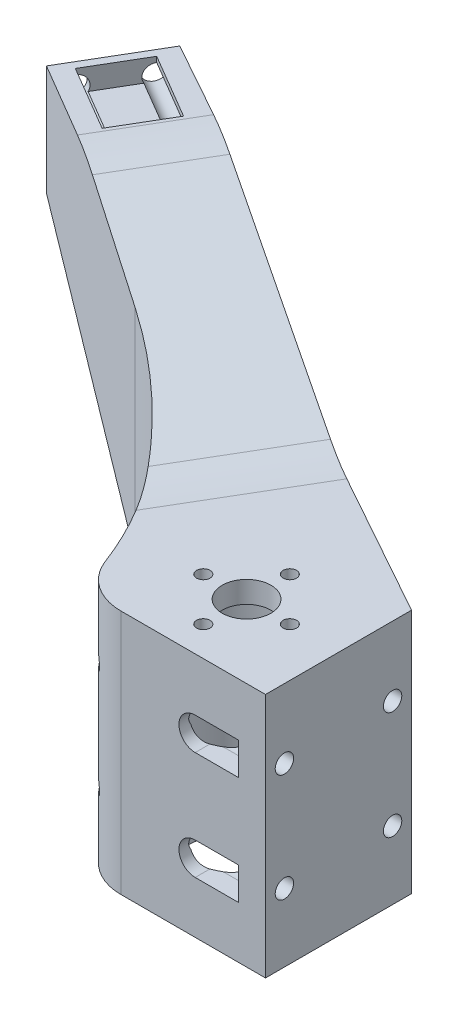
SolidWorks part; units mm, degrees
ref_plane "Front Plane" through (0, 0, 0) normal (0, 0, 1) x (1, 0, 0)
ref_plane "Top Plane" through (0, 0, 0) normal (0, 1, 0) x (1, 0, 0)
ref_plane "Right Plane" through (0, 0, 0) normal (1, 0, 0) x (0, 0, -1)
sketch "Sketch1" plane through (0, 0, 0) normal (0, 1, 0) x (1, 0, 0)
  line L0 (0, -1037.0992) -> (0, 50817.8602) construction
  line L1 (-1037.0992, 0) -> (50817.8602, 0) construction
  line L2 (39.2098, -13.5) -> (-39.2098, -13.5) construction
  line L4 (0, 0) -> (0, -27)
  line L7 (0, -13.5) -> (-43087.5168, 25353.1296) construction
  line L8 (-102.8226, 40.6517) -> (-97.2419, 50.131)
  line L9 (-102.8226, 40.6517) -> (-90.7581, 33.549)
  line L10 (-97.2419, 50.131) -> (-85.1774, 43.0283)
  line L11 (-90.7581, 33.549) -> (-85.1774, 43.0283)
  line L12 (-105.8909, 38.3966) -> (-96.7589, 53.9081)
  line L13 (0, 0) -> (-96.7589, 53.9081)
  line L14 (0, -27) -> (-34, -27)
  line L16 (-105.8909, 38.3966) -> (-40.525, -0.0858)
  line L17 (-40.525, -0.0858) -> (-34, -27)
  line L18 (-40.525, -0.0858) -> (-30.4777, 16.9803)
  circle A0 centre (-94, 41.84) radius 5.1855 construction
  circle A2 centre (-17, -13.5) radius 11.5 construction
  point P14 (0, -13.5)
  point P23 (-101.3249, 46.1523)
  dimension "D1" = 94
  dimension "D9" = 17
  dimension "D2" = 41.84
  dimension "D3" = 68.84
  dimension "D5" = 14
  dimension "D6" = 11
  dimension "D7" = 5.5
  dimension "D8" = 7
  dimension "D10" = 1.5
  dimension "D11" = 18
  dimension "D12" = 34
extrude "Boss-Extrude1" add sketch "Sketch1" against normal blind 60.4 contours L14 L4 L13 L12 L11 L9 L8 L10 | L9 L11 L10 L8 | L18 L17 L14 L4 L13 region at (-19.9485, 0, 8.3284) region at (-64.7476, 0, -25.2141) region at (-94, 0, -41.84)
sketch "Sketch2" plane through (0, 0, 0) normal (0, 1, 0) x (1, 0, 0)
  circle A0 centre (-17, -13.5) radius 11.5
extrude "Cut-Extrude1" cut sketch "Sketch2" against normal blind 55.4 from offset 19 offset against normal yes
sketch "Sketch4" plane through (0, 0, 0) normal (0, 1, 0) x (1, 0, 0)
  circle A0 centre (-17, -13.5) radius 4.5
extrude "Cut-Extrude3" cut sketch "Sketch4" against normal blind 55.4
sketch "Sketch6" plane through (-95.4228, 0, -56.1776) normal (-0.8618, 0, -0.5073) x (-0.5073, 0, 0.8618)
  line L0 (11.6336, -1000) -> (11.6336, 49000) construction
  line L1 (-7.9709, -3) -> (31.2381, -3) construction
  line L2 (0, 0) -> (23.2673, 0) construction
  circle A0 centre (6.1336, -3) radius 2
  circle A1 centre (17.1336, -3) radius 2
  point P6 (11.6336, -3)
  dimension "D2" = 5.5
  dimension "D1" = 3
extrude "Cut-Extrude5" cut sketch "Sketch6" against normal blind 20
sketch "Sketch7" plane through (0, 0, 0) normal (0, 1, 0) x (1, 0, 0)
  line L0 (-97.2419, 50.131) -> (-85.1774, 43.0283)
  line L1 (-97.2419, 50.131) -> (-102.8204, 40.6554)
  line L2 (-85.1774, 43.0283) -> (-90.7559, 33.5528)
  line L3 (-102.8204, 40.6554) -> (-90.7559, 33.5528)
extrude "Cut-Extrude6" cut sketch "Sketch7" against normal blind 4
hole_wizard "Tap Drill for M3x0.5 Tap1" positions "Sketch11" profile "Sketch12" hole size "M3x0.5" standard "ANSI Metric" end condition through all
sketch "Sketch11" plane through (0, 0, 0) normal (0, 1, 0) x (1, 0, 0)
  point P0 (-9, -13.5)
  point P12 (-17, -21.5)
  point P13 (-25, -13.5)
  point P14 (-17, -5.5)
  point P15 (-17, -13.5)
  dimension "D1" = 8
  dimension "D2" = 4
sketch "Sketch12" plane through (-9, 0, 13.5) normal (1, 0, 0) x (0, 0, 1)
  line L0 (0, 0) -> (0, 60.4)
  line L1 (0, 60.4) -> (1.25, 60.4)
  line L2 (1.25, 60.4) -> (1.25, 0)
  line L5 (1.25, 0) -> (0, 0)
  line L11 (0, -6.35) -> (0, 107.95) construction
  dimension "Thru Hole Dia." = 2.5
  dimension "Thru Hole Depth" = 60.4
extrude "Cut-Extrude7" cut sketch "Sketch1<5>" against normal blind 15 contours L18 L17 L14 L4 L13 region at (-19.9485, 0, 8.3284)
sketch "Sketch1<5>" plane through (0, 0, 0) normal (0, 1, 0) x (1, 0, 0) same geometry as "Sketch1"
sketch "Sketch13" plane through (-10.4681, 0, 17.781) normal (-0.5073, 0, 0.8618) x (0.8618, 0, 0.5073)
  line L0 (-34.8789, -15) -> (-34.8789, 0)
  line L1 (-34.8789, 0) -> (-90.6032, 0)
  line L2 (-90.6032, 0) -> (-34.8789, -15)
extrude "Cut-Extrude8" cut sketch "Sketch13" against normal through all
fillet "Fillet1" radius 70 1 edges at (-40.525, -37.7, 0.0858)
fillet "Fillet2" radius 10 1 edges at (-34, -37.7, 27)
chamfer "Chamfer1" distance 40 distance2 70 1 edges at (-101.3249, -60.4, -46.1523) first distance on face at (-103.1005, -3, -43.1362)
fillet "Fillet3" radius 30 3 edges at (-83.858, 0, -36.147) (-37.1661, -15, -5.6195) (-41.6324, -60.4, -9.5689)
hole_wizard "M3 Clearance Hole1" positions "Sketch14" profile "Sketch15" hole size "M3" standard "ANSI Metric" end condition through all
sketch "Sketch14" plane through (0, 0, 0) normal (1, 0, 0) x (0, 0, -1)
  line L0 (-27, -60.4) -> (-27, -15) construction
  line L1 (0, -60.4) -> (-27, -60.4) construction
  point P0 (-23.5, -47.8)
  point P5 (-3.5, -47.8)
  point P6 (-3.5, -27.8)
  point P7 (-23.5, -27.8)
  dimension "D3" = 3.5
  dimension "D4" = 12.6
  dimension "D1" = 2
  dimension "D2" = 2
sketch "Sketch15" plane through (0, -47.8, 23.5) normal (0, 1, 0) x (0, 0, -1)
  line L0 (0, 0) -> (0, 105.8909)
  line L1 (0, 105.8909) -> (1.7, 105.8909)
  line L2 (1.7, 105.8909) -> (1.7, 0)
  line L5 (1.7, 0) -> (0, 0)
  line L11 (0, -6.35) -> (0, 107.95) construction
  dimension "Thru Hole Dia." = 3.4
  dimension "Thru Hole Depth" = 105.8909
sketch "Sketch16" plane through (0, 0, 0) normal (1, 0, 0) x (0, 0, -1)
  line L0 (-23.5, -24.8) -> (-34.6393, -24.8)
  line L1 (-23.5, -50.8) -> (-34.6393, -50.8)
  line L3 (-23.5, -44.8) -> (-34.6393, -44.8)
  line L4 (-34.6393, -50.8) -> (-34.6393, -44.8)
  line L5 (-23.5, -30.8) -> (-34.6393, -30.8)
  line L6 (-34.6393, -30.8) -> (-34.6393, -24.8)
  line L7 (-13.5, -1010) -> (-13.5, 48990) construction
  line L8 (0, -15) -> (-27, -15) construction
  line L9 (7.6393, -30.8) -> (7.6393, -24.8)
  line L10 (-3.5, -30.8) -> (7.6393, -30.8)
  line L11 (7.6393, -50.8) -> (7.6393, -44.8)
  line L12 (-3.5, -44.8) -> (7.6393, -44.8)
  line L13 (-3.5, -50.8) -> (7.6393, -50.8)
  line L14 (-3.5, -24.8) -> (7.6393, -24.8)
  arc A0 (-23.5, -50.8) -> (-23.5, -44.8) centre (-23.5, -47.8) ccw
  arc A1 (-23.5, -30.8) -> (-23.5, -24.8) centre (-23.5, -27.8) ccw
  arc A2 (-3.5, -30.8) -> (-3.5, -24.8) centre (-3.5, -27.8) cw
  arc A3 (-3.5, -50.8) -> (-3.5, -44.8) centre (-3.5, -47.8) cw
  point P16 (-13.5, -15)
  dimension "D2" = 3
  dimension "D1" = 2
extrude "Cut-Extrude9" cut sketch "Sketch16" against normal blind 8 from offset 5 offset against normal yes
sketch "Sketch19" plane through (0, 0, 27) normal (0, 0, 1) x (1, 0, 0)
  line L0 (-13, -24.8) -> (-13, -30.8) construction
  line L1 (-13, -44.8) -> (-13, -50.8) construction
  circle A0 centre (-13, -27.8) radius 3
  circle A1 centre (-13, -47.8) radius 3
extrude "Cut-Extrude10" cut sketch "Sketch19" against normal through all
hole_wizard "CSK for M2 Flat Head Machine Screw1" positions "Sketch20" profile "Sketch22" countersink size "M2" standard "ANSI Metric"
sketch "Sketch20" plane through (-95.4228, 0, -56.1776) normal (-0.8618, 0, -0.5073) x (-0.5073, 0, 0.8618)
  line L0 (20.6336, 0) -> (2.6336, 0) construction
  point P0 (11.6336, -11)
  point P4 (11.6336, -10.3613)
  dimension "D1" = 11
sketch "Sketch22" plane through (-101.3249, -11, -46.1523) normal (0, 1, 0) x (-0.5073, 0, 0.8618)
  line L0 (0, 0) -> (0, 7.5186)
  line L1 (0, 7.5186) -> (2.5273, 6)
  line L2 (2.5273, 6) -> (2.5273, 0.3895)
  line L3 (2.5273, 0.3895) -> (2.8, 0)
  line L5 (2.8, 0) -> (0, 0)
  line L6 (-2.5273, 0.3895) -> (-2.8, 0) construction
  line L10 (0, 7.5186) -> (-2.5273, 6) construction
  line L11 (0, -6.35) -> (0, 107.95) construction
  dimension "Hole Dia." = 5.0546
  dimension "Hole Depth" = 6
  dimension "Near C'Sink Dia." = 5.6
  dimension "Near C'Sink Angle" = 70
  dimension "Drill Angle" = 118
